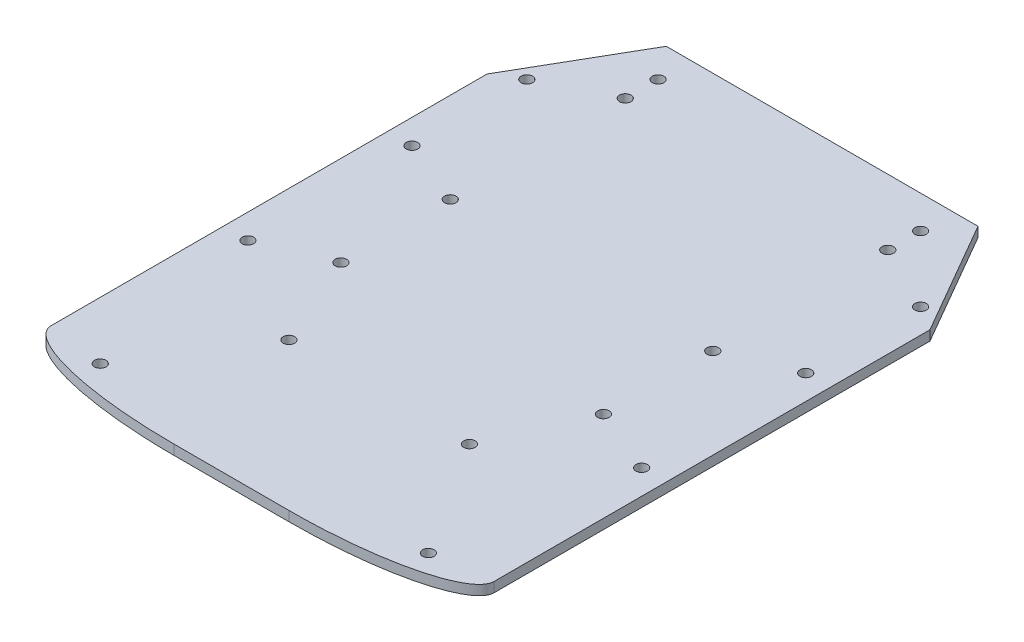
SolidWorks part; units mm, degrees
material "Balsa"
ref_plane "Alzado" through (0, 0, 0) normal (0, 0, 1) x (1, 0, 0)
ref_plane "Planta" through (0, 0, 0) normal (0, 1, 0) x (1, 0, 0)
ref_plane "Vista lateral" through (0, 0, 0) normal (1, 0, 0) x (0, 0, -1)
sketch "Sketch2" plane through (0, 0, 0) normal (0, 1, 0) x (1, 0, 0)
  line L1 (-67.5, 90) -> (67.5, 90)
  line L2 (-67.5, 90) -> (-67.5, -90)
  line L3 (-67.5, -90) -> (67.5, -90)
  line L4 (67.5, 90) -> (67.5, -90)
  line L5 (-67.5, 90) -> (67.5, -90) construction
  line L6 (-67.5, -90) -> (67.5, 90) construction
  point P0 (0, 0)
  dimension "D1" = 135
  dimension "D2" = 180
extrude "Boss-Extrude2" add sketch "Sketch2" along normal blind 3
sketch "Sketch3" plane through (0, 3, 0) normal (0, 1, 0) x (1, 0, 0)
  line L0 (0, -90) -> (0, 90) construction
  line L1 (-67.5, -90) -> (67.5, -90) construction
  line L2 (67.5, 90) -> (-67.5, 90) construction
  line L3 (-67.5, 90) -> (-67.5, -90) construction
  line L4 (-67.5, -90) -> (67.5, -90) construction
  circle A0 centre (-27.5, -45) radius 1.75
  circle A1 centre (27.5, -45) radius 1.75
  circle A2 centre (-50, -80) radius 1.75
  circle A3 centre (50, -80) radius 1.75
  dimension "D1" = 40
  dimension "D3" = 3.5
  dimension "D4" = 10
  dimension "D2" = 45
  dimension "D5" = 50
extrude "Cut-Extrude1" cut sketch "Sketch3" against normal through all
fillet "Fillet1" radius 12.5 1 edges at (-67.5, 1.5, 90) second distance 50 first distance on face at (-67.5, 1.5, 0)
fillet "Fillet2" radius 12.5 1 edges at (67.5, 1.5, 90) second distance 50 first distance on face at (67.5, 1.5, 0)
chamfer "Chamfer2" distance 20 angle 60 1 edges at (67.5, 1.5, -90) first distance on face at (0, 1.5, -90)
chamfer "Chamfer3" distance 20 angle 60 1 edges at (-67.5, 1.5, -90) first distance on face at (-10, 1.5, -90)
sketch "Sketch4" plane through (0, 3, 0) normal (0, 1, 0) x (1, 0, 0)
  line L0 (0, 90) -> (0, 0) construction
  line L1 (47.5, 90) -> (-47.5, 90) construction
  circle A0 centre (-40, 80) radius 1.75
  circle A1 centre (-60, 60) radius 1.75
  circle A2 centre (60, 60) radius 1.75
  circle A3 centre (40, 80) radius 1.75
  dimension "D1" = 3.5
  dimension "D2" = 10
  dimension "D3" = 30
  dimension "D4" = 40
  dimension "D5" = 60
extrude "Cut-Extrude2" cut sketch "Sketch4" against normal through all
sketch "Sketch5" plane through (0, 3, 0) normal (0, 1, 0) x (1, 0, 0)
  line L0 (0, 90) -> (0, -90) construction
  line L1 (47.5, 90) -> (-47.5, 90) construction
  line L2 (-17.5, -90) -> (17.5, -90) construction
  circle A0 centre (-40, 70) radius 1.75
  circle A1 centre (40, 70) radius 1.75
  dimension "D1" = 20
  dimension "D3" = 3.5
  dimension "D2" = 40
extrude "Cut-Extrude3" cut sketch "Sketch5" against normal through all
sketch "Sketch6" plane through (0, 3, 0) normal (0, 1, 0) x (1, 0, 0)
  line L0 (0, 90) -> (0, -90) construction
  line L5 (47.5, 90) -> (-47.5, 90) construction
  line L6 (-17.5, -90) -> (17.5, -90) construction
  line L7 (-67.5, 0) -> (67.5, 0) construction
  line L8 (-67.5, 55.359) -> (-67.5, -77.5) construction
  line L9 (67.5, -77.5) -> (67.5, 55.359) construction
  line L11 (-60, 25) -> (60, 25) construction
  line L12 (-60, 25) -> (-60, -25) construction
  line L13 (-60, -25) -> (60, -25) construction
  line L14 (60, 25) -> (60, -25) construction
  line L15 (-60, 25) -> (60, -25) construction
  line L16 (-60, -25) -> (60, 25) construction
  circle A0 centre (-60, 25) radius 1.75
  circle A1 centre (60, 25) radius 1.75
  circle A2 centre (60, -25) radius 1.75
  circle A3 centre (-60, -25) radius 1.75
  circle A4 centre (-40, 16.6667) radius 1.75
  circle A5 centre (40, 16.6667) radius 1.75
  circle A6 centre (40, -16.6667) radius 1.75
  circle A7 centre (-40, -16.6667) radius 1.75
  point P14 (0, 0)
  dimension "D1" = 3.5
  dimension "D2" = 120
  dimension "D3" = 50
  dimension "D4" = 40
extrude "Cut-Extrude4" cut sketch "Sketch6" against normal through all
